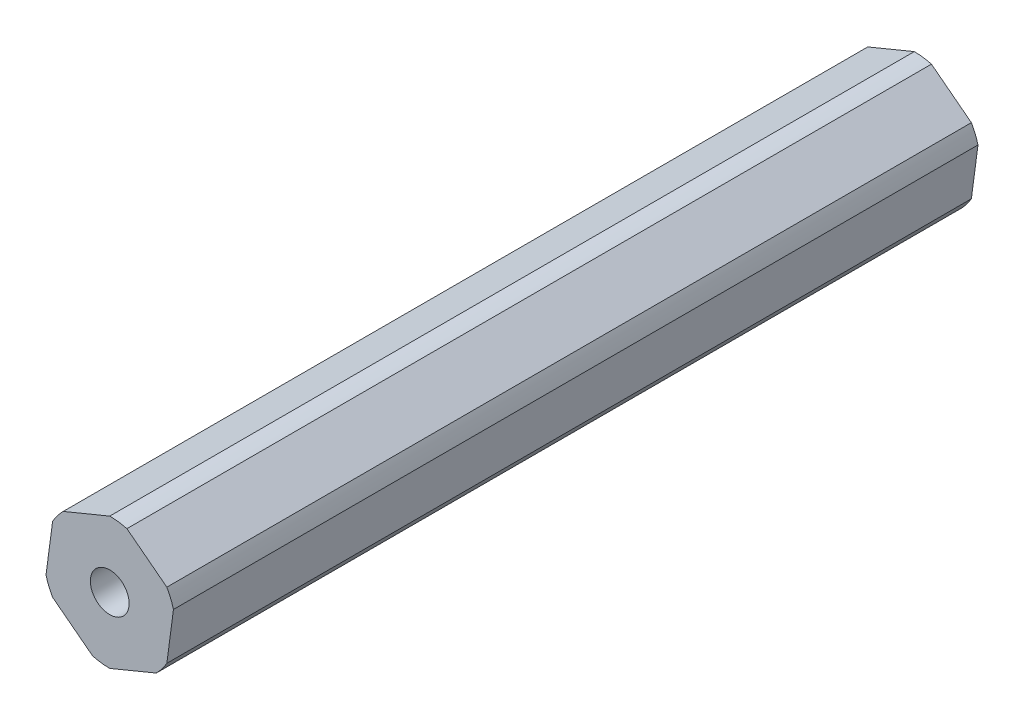
SolidWorks part; units mm, degrees
ref_plane "Front Plane" through (0, 0, 0) normal (0, 0, 1) x (1, 0, 0)
ref_plane "Top Plane" through (0, 0, 0) normal (0, 1, 0) x (1, 0, 0)
ref_plane "Right Plane" through (0, 0, 0) normal (1, 0, 0) x (0, 0, -1)
sketch "Sketch1" plane through (0, 0, 0) normal (0, 0, 1) x (1, 0, 0)
  line L1 (5.9502, 3.4353) -> (1.7899, 6.6335)
  line L2 (0, 6.8707) -> (-4.8498, 4.8668)
  line L3 (-5.9502, 3.4353) -> (-6.6397, -1.7666)
  line L4 (-5.9502, -3.4354) -> (-1.7899, -6.6335)
  line L5 (0, -6.8707) -> (4.8498, -4.8668)
  line L6 (5.9502, -3.4354) -> (6.6397, 1.7666)
  circle A0 centre (0, 0) radius 6.35 construction
  arc A1 (1.7899, 6.6335) -> (0, 6.8707) centre (0, 0) ccw
  arc A2 (6.6397, 1.7666) -> (5.9502, 3.4353) centre (0, 0) ccw
  arc A3 (4.8498, -4.8668) -> (5.9502, -3.4354) centre (0, 0) ccw
  arc A4 (-1.7899, -6.6335) -> (0, -6.8707) centre (0, 0) ccw
  arc A5 (-6.6397, -1.7666) -> (-5.9502, -3.4354) centre (0, 0) ccw
  arc A6 (-4.8498, 4.8668) -> (-5.9502, 3.4353) centre (0, 0) ccw
  dimension "D1" = 13.7414
  dimension ".5" = 12.7
extrude "Boss-Extrude1" add sketch "Sketch1" along normal blind 83.82
hole_wizard "#10-32 Tapped Hole1" positions "Sketch3" profile "Sketch4" tap size "#10-32" standard "ANSI Inch"
sketch "Sketch3" plane through (0, 0, 83.82) normal (0, 0, 1) x (1, 0, 0)
  point P0 (0, 0)
sketch "Sketch4" plane through (0, 0, 83.82) normal (1, 0, 0) x (0, -1, 0)
  line L0 (0, 0) -> (0, 13.2529)
  line L1 (0, 13.2529) -> (2.0193, 12.0396)
  line L2 (2.0193, 12.0396) -> (2.0193, 0)
  line L5 (2.0193, 0) -> (0, 0)
  line L10 (0, 13.2529) -> (-2.0193, 12.0396) construction
  line L11 (0, -6.35) -> (0, 107.95) construction
  dimension "Tap Drill Dia." = 4.0386
  dimension "Tap Drill Depth" = 12.0396
  dimension "Drill Angle" = 118
cosmetic thread "Hole Thread1" parameters "D1"=9.652, "D2"=4.826
hole_wizard "#10-32 Tapped Hole2" positions "Sketch6" profile "Sketch5" tap size "#10-32" standard "ANSI Inch"
sketch "Sketch6" plane through (0, 0, 0) normal (0, 0, -1) x (-1, 0, 0)
  point P0 (0, 0)
sketch "Sketch5" plane through (0, 0, 0) normal (1, 0, 0) x (0, 1, 0)
  line L0 (0, 0) -> (0, 13.2529)
  line L1 (0, 13.2529) -> (2.0193, 12.0396)
  line L2 (2.0193, 12.0396) -> (2.0193, 0)
  line L5 (2.0193, 0) -> (0, 0)
  line L10 (0, 13.2529) -> (-2.0193, 12.0396) construction
  line L11 (0, -6.35) -> (0, 107.95) construction
  dimension "Tap Drill Dia." = 4.0386
  dimension "Tap Drill Depth" = 12.0396
  dimension "Drill Angle" = 118
cosmetic thread "Hole Thread2" parameters "D1"=9.652, "D2"=4.826
